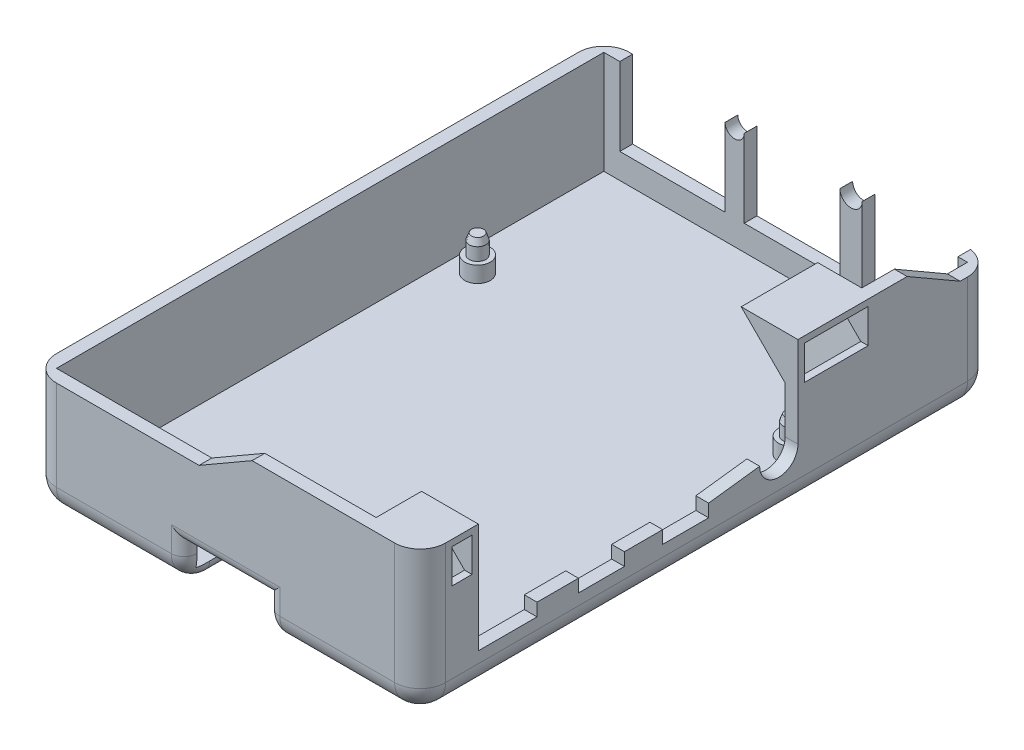
SolidWorks part; units mm, degrees
ref_plane "Płaszczyzna przednia" through (0, 0, 0) normal (0, 0, 1) x (1, 0, 0)
ref_plane "Płaszczyzna górna" through (0, 0, 0) normal (0, 1, 0) x (1, 0, 0)
ref_plane "Płaszczyzna prawa" through (0, 0, 0) normal (1, 0, 0) x (0, 0, -1)
sketch "Szkic1" plane through (0, 0, 0) normal (0, 1, 0) x (1, 0, 0)
  line L0 (-28.5, 42.9) -> (-30.5, 42.9) construction
  line L1 (-28.1, -42.5) -> (28.1, -42.5)
  line L2 (-28.1, -42.5) -> (-28.1, 42.5)
  line L3 (-28.1, 42.5) -> (28.1, 42.5)
  line L4 (28.1, -42.5) -> (28.1, 42.5)
  line L5 (-28.1, -42.5) -> (28.1, 42.5) construction
  line L6 (-28.1, 42.5) -> (28.1, -42.5) construction
  line L7 (28.5, -42.9) -> (-28.5, -42.9)
  line L8 (28.5, -42.9) -> (28.5, 42.9)
  line L9 (28.5, 42.9) -> (-28.5, 42.9)
  line L10 (-28.5, -42.9) -> (-28.5, 42.9)
  line L11 (28.5, -42.9) -> (-28.5, 42.9) construction
  line L12 (28.5, 42.9) -> (-28.5, -42.9) construction
  line L13 (30.5, -44.9) -> (-30.5, -44.9)
  line L14 (30.5, -44.9) -> (30.5, 44.9)
  line L15 (30.5, 44.9) -> (-30.5, 44.9)
  line L16 (-30.5, -44.9) -> (-30.5, 44.9)
  line L17 (30.5, -44.9) -> (-30.5, 44.9) construction
  line L18 (30.5, 44.9) -> (-30.5, -44.9) construction
  line L19 (-28.5, 42.9) -> (-28.5, 44.9) construction
  line L20 (-28.1, 42.5) -> (-28.1, 42.9) construction
  line L21 (-28.1, 42.5) -> (-28.5, 42.5) construction
  point P0 (0, 0)
  point P6 (0, 0)
  point P12 (0, 0)
  dimension "D1" = 56.2
  dimension "D2" = 85
  dimension "D3" = 2
  dimension "D4" = 0.4
extrude "Dodanie-wyciągnięcie2" add sketch "Szkic1" along normal blind 2 contours L1 L4 L3 L2 region at (0, 0, 0)
sketch "Szkic2" plane through (0, 2, 0) normal (0, 1, 0) x (1, 0, 0)
  line L0 (-24.575, -40.975) -> (-24.575, -42.5) construction
  line L1 (-28.1, -42.5) -> (28.1, -42.5) construction
  line L2 (-26.575, -38.975) -> (-28.1, -38.975) construction
  line L3 (-28.1, -42.5) -> (-28.1, 42.5) construction
  line L4 (24.575, -40.975) -> (24.575, -42.5) construction
  line L5 (26.575, -38.975) -> (28.1, -38.975) construction
  line L6 (28.1, -42.5) -> (28.1, 42.5) construction
  line L7 (-26.575, 19.175) -> (-28.1, 19.175) construction
  line L8 (26.575, 19.175) -> (28.1, 19.175) construction
  line L9 (-24.575, 19.175) -> (24.575, 19.175) construction
  line L10 (24.575, 19.175) -> (24.575, -38.975) construction
  circle A0 centre (-24.575, -38.975) radius 2
  circle A1 centre (24.575, -38.975) radius 2
  circle A2 centre (-24.575, 19.175) radius 2
  circle A3 centre (24.575, 19.175) radius 2
  dimension "D2" = 4
  dimension "D3" = 3.525
  dimension "D1" = 58.15
extrude "Dodanie-wyciągnięcie5" add sketch "Szkic2" along normal blind 2.5 contours A2 | A3 | A1 | A0
sketch "Szkic4" plane through (0, 4.5, 0) normal (0, 1, 0) x (1, 0, 0)
  line L0 (0, -38.975) -> (0, 19.175) construction
  line L1 (-24.575, -38.975) -> (24.575, -38.975) construction
  line L2 (-24.575, -38.975) -> (-24.575, 19.175) construction
  line L3 (-24.575, 19.175) -> (24.575, 19.175) construction
  line L4 (24.575, -38.975) -> (24.575, 19.175) construction
  line L5 (24.575, -9.9) -> (-24.575, -9.9) construction
  circle A0 centre (-24.575, 19.175) radius 1.3
  point P8 (0, -8.6)
  point P15 (0, -9.9)
  dimension "D1" = 2.6
extrude "Dodanie-wyciągnięcie6" add sketch "Szkic4" along normal blind 2 contours A0 | A0 region at (-24.575, 4.5, -19.175)
sketch "Szkic6" plane through (0, 6.5, 0) normal (0, 1, 0) x (1, 0, 0)
  circle A0 centre (-24.575, 19.175) radius 1.3
  circle A1 centre (-24.575, 19.175) radius 1.3 construction
  circle M3 centre (-24.575, 19.175) radius 1.3
extrude "Dodanie-wyciągnięcie7" add sketch "Szkic6" along normal blind 1 draft 20 contours M3 | A0 region at (-24.575, 6.5, -19.175)
extrude "Dodanie-wyciągnięcie3" add sketch "Szkic1<4>" along normal up to surface (2 mm away) contours L10 L7 L8 L9 L4 L1 L2 L3 region at (0, 0, 42.797) up to face at (-24.575, 2, 40.975)
sketch "Szkic1<4>" plane through (0, 0, 0) normal (0, 1, 0) x (1, 0, 0) same geometry as "Szkic1"
extrude "Dodanie-wyciągnięcie4" add sketch "Szkic1<5>" along normal up to surface (4.5 mm away) contours L16 L13 L14 L15 L7 L10 L9 L8 region at (0, 0, 43.8144) up to face at (-24.575, 4.5, 40.975)
sketch "Szkic1<5>" plane through (0, 0, 0) normal (0, 1, 0) x (1, 0, 0) same geometry as "Szkic1"
mirror "Lustro1" about plane through (0, 0, 0) normal (1, 0, 0) of "Dodanie-wyciągnięcie7", "Dodanie-wyciągnięcie6"
ref_plane "Płaszczyzna miedzy kolkami" through (0, 0, 9.9) normal (0, 0, 1) x (1, 0, 0)
mirror "Lustro2" about plane through (0, 0, 9.9) normal (0, 0, 1) of "Dodanie-wyciągnięcie7", "Lustro1", "Dodanie-wyciągnięcie6"
sketch "Szkic12" plane through (0, 0, 44.9) normal (0, 0, 1) x (1, 0, 0)
  line L0 (30.5, 0) -> (-30.5, 0) construction
  line L1 (-6.5, 0) -> (6.5, 0)
  line L2 (-6.5, 0) -> (-6.5, 4.5)
  line L3 (-6.5, 4.5) -> (6.5, 4.5)
  line L4 (6.5, 0) -> (6.5, 4.5)
  line L5 (30.5, 4.5) -> (-30.5, 4.5) construction
  line L6 (-6.5, 2.25) -> (-30.5, 2.25) construction
  line L7 (-30.5, 4.5) -> (-30.5, 0) construction
  line L8 (6.5, 2.25) -> (30.5, 2.25) construction
  line L9 (30.5, 4.5) -> (30.5, 0) construction
  dimension "D1" = 13
extrude "Wytnij-wyciągnięcie4" cut sketch "Szkic12" against normal blind 10
sketch "Szkic13" plane through (0, 4.5, 0) normal (0, 1, 0) x (1, 0, 0)
  line L12 (-6.5, -44.9) -> (-6.5, -42.9)
  line L13 (-6.5, -42.9) -> (-28.5, -42.9)
  line L14 (-28.5, -42.9) -> (-28.5, 42.9)
  line L15 (-28.5, 42.9) -> (28.5, 42.9)
  line L16 (28.5, 42.9) -> (28.5, -42.9)
  line L17 (28.5, -42.9) -> (6.5, -42.9)
  line L18 (6.5, -42.9) -> (6.5, -44.9)
  line L19 (6.5, -44.9) -> (30.5, -44.9)
  line L20 (30.5, -44.9) -> (30.5, 44.9)
  line L21 (30.5, 44.9) -> (-30.5, 44.9)
  line L22 (-30.5, 44.9) -> (-30.5, -44.9)
  line L23 (-30.5, -44.9) -> (-6.5, -44.9)
  line L24 (-6.5, -44.9) -> (-6.5, -42.9)
  line L25 (-6.5, -42.9) -> (-28.5, -42.9)
  line L26 (-28.5, -42.9) -> (-28.5, 42.9)
  line L27 (-28.5, 42.9) -> (28.5, 42.9)
  line L28 (28.5, 42.9) -> (28.5, -42.9)
  line L29 (28.5, -42.9) -> (6.5, -42.9)
  line L30 (6.5, -42.9) -> (6.5, -44.9)
  line L31 (6.5, -44.9) -> (30.5, -44.9)
  line L32 (30.5, -44.9) -> (30.5, 44.9)
  line L33 (30.5, 44.9) -> (-30.5, 44.9)
  line L34 (-30.5, 44.9) -> (-30.5, -44.9)
  line L35 (-30.5, -44.9) -> (-6.5, -44.9)
  dimension "D1" = 0
extrude "Dodanie-wyciągnięcie8" add sketch "Szkic13" along normal blind 1.45 contours L24 L25 L26 L27 L28 L29 L30 L31 L32 L33 L34 L35
sketch "Szkic14" plane through (0, 5.95, 0) normal (0, 1, 0) x (1, 0, 0)
  line L1 (-30.5, -44.9) -> (30.5, -44.9)
  line L2 (-30.5, -44.9) -> (-30.5, 44.9)
  line L3 (-30.5, 44.9) -> (30.5, 44.9)
  line L4 (30.5, -44.9) -> (30.5, 44.9)
  line L5 (-28.5, -42.9) -> (28.5, -42.9)
  line L6 (-28.5, -42.9) -> (-28.5, 42.9)
  line L7 (-28.5, 42.9) -> (28.5, 42.9)
  line L8 (28.5, -42.9) -> (28.5, 42.9)
extrude "Dodanie-wyciągnięcie9" add sketch "Szkic14" along normal blind 17
sketch "Szkic15" plane through (0, 0, -44.9) normal (0, 0, -1) x (-1, 0, 0)
  line L0 (-30.5, 22.95) -> (30.5, 22.95) construction
  line L1 (-27, 22.95) -> (26, 22.95)
  line L2 (-27, 22.95) -> (-27, 5.95)
  line L3 (-27, 5.95) -> (26, 5.95)
  line L4 (26, 22.95) -> (26, 5.95)
  line L5 (-27, 5.95) -> (-30.5, 5.95) construction
  line L6 (-30.5, 22.95) -> (-30.5, 0) construction
  line L7 (9.5, 5.95) -> (9.5, 22.95)
  line L8 (30.5, 22.95) -> (30.5, 0) construction
  line L9 (-30.5, 4.5) -> (30.5, 4.5) construction
  line L10 (-22.575, 4.5) -> (-26.575, 4.5) construction
  line L11 (6.5, 5.95) -> (6.5, 22.95)
  line L12 (-12, 5.95) -> (-12, 22.95)
  line L13 (-8.5, 5.95) -> (-8.5, 22.95)
  line L14 (-27, 14.45) -> (-12, 14.45) construction
  line L15 (-8.5, 14.45) -> (6.5, 14.45) construction
  line M9 (30.5, 22.95) -> (-30.5, 22.95)
  dimension "D1" = 3.5
  dimension "D2" = 1.45
  dimension "D3" = 4.5
  dimension "D4" = 16.5
  dimension "D5" = 15
  dimension "D6" = 3.5
extrude "Wytnij-wyciągnięcie5" cut sketch "Szkic15" against normal up to surface (2 mm away) contours L7 L3 L4 M9 | L13 L3 L11 M9 | L3 L12 L1 L2 region at (19.5, 14.45, -44.9) region at (1, 14.45, -44.9) region at (-17.75, 14.45, -44.9) up to face at (0, 12.475, -42.9)
sketch "Szkic16" plane through (30.5, 0, 0) normal (1, 0, 0) x (0, 0, -1)
  line L0 (-44.9, 22.95) -> (44.9, 22.95) construction
  line L1 (-36.975, 22.95) -> (17.175, 22.95)
  line L2 (-36.975, 22.95) -> (-36.975, 5.75)
  line L3 (-36.975, 5.75) -> (17.175, 5.75)
  line L4 (17.175, 22.95) -> (17.175, 5.75)
  line L5 (-36.975, 2) -> (-36.975, 4.5) construction
  line L6 (17.175, 4.5) -> (17.175, 2) construction
  line L7 (-36.975, 5.75) -> (-36.975, 4.5) construction
  line L8 (-36.975, 4.5) -> (17.175, 4.5) construction
  line L9 (17.175, 4.5) -> (17.175, 5.75) construction
  line L10 (21.175, 4.5) -> (17.175, 4.5) construction
  line L11 (-35.775, 5.75) -> (-35.775, 22.95)
  line L12 (-26.575, 5.75) -> (-26.575, 22.95)
  line L13 (-20.075, 5.75) -> (-20.075, 22.95)
  line L14 (-12.875, 5.75) -> (-12.875, 22.95)
  line L15 (-6.875, 5.75) -> (-6.875, 22.95)
  line L16 (0.325, 5.75) -> (0.325, 22.95)
  line L17 (8.325, 5.75) -> (8.325, 22.95)
  line L18 (14.325, 5.75) -> (14.325, 22.95)
  line L19 (17.175, 5.75) -> (-36.975, 5.75) construction
  line L20 (17.175, 11.75) -> (-36.975, 11.75)
  line L21 (-36.975, 9.75) -> (17.175, 9.75)
  line L22 (-36.975, 7.75) -> (17.175, 7.75)
  line L23 (-37.975, 7.75) -> (-37.975, 9.75) construction
  line L24 (-37.975, 7.75) -> (-37.975, 5.75) construction
  line L25 (0.325, 7.75) -> (8.325, 8.75)
  circle A0 centre (11.325, 8.75) radius 3
  point P42 (0.325, 7.75)
  dimension "D1" = 1.25
  dimension "D2" = 9.2
  dimension "D3" = 7.2
  dimension "D4" = 7.2
  dimension "D5" = 6
  dimension "D6" = 1.2
  dimension "D7" = 6.5
  dimension "D8" = 6
  dimension "D9" = 8
  dimension "D10" = 0
  dimension "D11" = 4
  dimension "D12" = 1
extrude "Wytnij-wyciągnięcie6" cut sketch "Szkic16" against normal up to surface (2 mm away) contours L20 L12 L1 L11 | L11 L21 L12 L20 | L11 L22 L12 L21 | L22 L11 L3 L12 | L20 L14 L1 L13 | L13 L21 L14 L20 | L13 L22 L14 L21 | L22 L13 L3 L14 | L20 L16 L1 L15 | L15 L21 L16 L20 | L15 L22 L16 L21 | L22 L15 L3 L16 | L20 L17 L1 L16 | L16 L21 L17 L20 | L16 L25 L17 L21 | L20 L15 L1 L14 | L14 L21 L15 L20 | L14 L22 L15 L21 | L20 L13 L1 L12 | L12 L21 L13 L20 | L12 L22 L13 L21 | L21 A0 L22 | L21 A0 | L22 A0 | A0 L20 L17 L21 | A0 L21 L18 L20 | L20 L18 L1 L17 | A0 L18 L21 | A0 L21 L17 region at (30.5, 17.35, 31.175) region at (30.5, 17.35, 23.325) region at (30.5, 10.75, 31.175) region at (30.5, 17.35, 16.475) region at (30.5, 10.75, 23.325) region at (30.5, 8.75, 31.175) region at (30.5, 17.35, 9.875) region at (30.5, 10.75, 16.475) region at (30.5, 8.75, 23.325) region at (30.5, 6.75, 31.175) region at (30.5, 17.35, 3.275) region at (30.5, 10.75, 9.875) region at (30.5, 8.75, 16.475) region at (30.5, 17.35, -4.325) region at (30.5, 10.75, 3.275) region at (30.5, 8.75, 9.875) region at (30.5, 6.75, 16.475) region at (30.5, 17.35, -11.325) region at (30.5, 10.75, -4.325) region at (30.5, 8.75, 3.275) region at (30.5, 11.1275, -9.0138) region at (30.5, 8.9722, -3.8806) region at (30.5, 6.75, 3.275) region at (30.5, 11.1275, -13.6362) region at (30.5, 9.5015, -8.3762) region at (30.5, 10.5784, -11.325) region at (30.5, 9.5015, -14.2738) region at (30.5, 8.75, -11.325) region at (30.5, 6.9216, -11.325) up to face at (28.5, 12.475, 0)
sketch "Szkic17" plane through (-30.5, 0, 0) normal (-1, 0, 0) x (0, 0, 1)
  line L0 (-44.9, 22.95) -> (44.9, 22.95) construction
  line L1 (-42.9, 22.95) -> (44.9, 22.95)
  line L2 (-42.9, 22.95) -> (-42.9, 2)
  line L3 (-42.9, 2) -> (44.9, 2)
  line L4 (44.9, 22.95) -> (44.9, 2)
  line L5 (44.9, 22.95) -> (44.9, 0) construction
  line L6 (-42.9, 22.95) -> (-42.9, 2) construction
  line L8 (34.9, 2) -> (42.9, 2) construction
extrude "Wytnij-wyciągnięcie7" [suppressed] cut sketch "Szkic17" against normal up to surface (2 mm away) up to face at (-28.5, 12.475, 0)
fillet "Zaokrąglenie1" radius 4 9 edges at (-18.5, 0, 44.9) (18.5, 0, 44.9) (30.5, 0, 0) (-30.5, 0, 0) (0, 0, -44.9) (-30.5, 11.475, -44.9) (30.5, 11.475, -44.9) (30.5, 11.475, 44.9) (-30.5, 11.475, 44.9)
fillet "Zaokrąglenie2" radius 2 8 edges at (6.5, 4.975, 44.9) (-6.5, 4.975, 44.9) (-6.5, 0, 37.9) (0, 5.95, 44.9) (6.5, 0, 37.9) (6.5, 1.1716, 43.7284) (-6.5, 1.1716, 43.7284) (0, 0, 34.9)
sketch "Szkic18" plane through (0, 0, -14.325) normal (0, 0, 1) x (1, 0, 0)
  line L0 (28.5, 22.95) -> (21.6, 22.95)
  line L1 (21.6, 22.95) -> (28.5, 16.05)
  line L2 (28.5, 8.75) -> (28.5, 22.95) construction
  line L3 (28.5, 16.05) -> (28.5, 22.95)
  dimension "D1" = 6.9
  dimension "D2" = 45
extrude "Dodanie-wyciągnięcie10" add sketch "Szkic18" against normal blind 12
sketch "Szkic19" plane through (30.5, 0, 0) normal (1, 0, 0) x (0, 0, -1)
  line L0 (14.325, 21.95) -> (15.325, 21.95)
  line L1 (14.325, 8.75) -> (14.325, 22.95) construction
  line L2 (15.325, 21.95) -> (15.325, 22.95)
  line L3 (14.325, 22.95) -> (40.9, 22.95) construction
  line L5 (15.325, 21.95) -> (25.325, 21.95)
  line L6 (15.325, 21.95) -> (15.325, 16.6161)
  line L7 (15.325, 16.6161) -> (25.325, 16.6161)
  line L8 (25.325, 21.95) -> (25.325, 16.6161)
  dimension "D1" = 1
  dimension "D2" = 10
extrude "Wytnij-wyciągnięcie8" cut sketch "Szkic19" along direction (-1, 0, 0) on the side against the normal up to vertex (8.9 mm away) contours L8 L5 L6 L7 region at (30.5, 19.283, -20.325) up to point (21.6, 22.95, -14.325)
sketch "Szkic20" plane through (0, 0, -25.325) normal (0, 0, 1) x (1, 0, 0)
  line L4 (30.5, 11.95) -> (22.6, 11.95)
  line L6 (24.0142, 21.95) -> (29.3481, 16.6161)
  line L7 (23.3071, 22.6571) -> (28.641, 17.3232) construction
  line L8 (27.9339, 16.6161) -> (30.5, 16.6161)
  line L9 (30.5, 16.6161) -> (30.5, 21.95)
  line L10 (30.5, 21.95) -> (22.6, 21.95)
  line L11 (22.6, 21.95) -> (27.9339, 16.6161)
  line L12 (27.9339, 16.6161) -> (30.5, 16.6161)
  line L13 (30.5, 16.6161) -> (30.5, 21.95)
  line L14 (30.5, 21.95) -> (22.6, 21.95)
  line L15 (22.6, 21.95) -> (27.9339, 16.6161)
  line M6 (27.9339, 16.6161) -> (30.5, 16.6161)
  line M8 (30.5, 21.95) -> (22.6, 21.95)
  line M9 (22.6, 21.95) -> (27.9339, 16.6161)
  dimension "D1" = 0
  dimension "D2" = 10
  dimension "D3" = 1
extrude "Dodanie-wyciągnięcie11" add sketch "Szkic20" along normal up to surface (10 mm away) contours L6 M8 M9 M6 region at (25.9741, 19.283, -25.325) up to face at (27.8835, 19.283, -15.325)
sketch "Szkic22" plane through (0, 0, -44.9) normal (0, 0, -1) x (-1, 0, 0)
  line L1 (9.5, 5.95) -> (9.5, 22.95) construction
  line L3 (6.5, 22.95) -> (9.5, 22.95) construction
  line L4 (9.5, 22.95) -> (6.5, 22.95)
  line L5 (9.5, 18.1544) -> (9.5, 22.95)
  line L7 (30.5, 22.95) -> (30.5, 4) construction
  line L10 (28.5, 22.95) -> (-28.5, 22.95) construction
  line L12 (-8.5, 18.1544) -> (-12, 18.1544) construction
  line L13 (-8.5, 5.95) -> (-8.5, 22.95) construction
  line L14 (-12, 5.95) -> (-12, 22.95) construction
  line L15 (-8.5, 18.1544) -> (6.5, 18.1544)
  line L16 (6.5, 5.95) -> (6.5, 22.95) construction
  line L17 (6.5, 18.1544) -> (9.5, 18.1544)
  line L18 (9.5, 18.1544) -> (26, 18.1544)
  line L19 (26, 22.95) -> (26, 5.95) construction
  line L20 (26, 18.1544) -> (30.5, 18.1544)
  line L21 (-12, 18.1544) -> (-12, 22.95)
  line L22 (-12, 22.95) -> (-8.5, 22.95)
  line L23 (-8.5, 22.95) -> (-8.5, 18.1544)
  line L24 (6.5, 18.1544) -> (6.5, 22.95)
  line L25 (30.5, 18.1544) -> (30.5, 22.95)
  line L26 (30.5, 22.95) -> (26.5, 22.95) construction
  line L27 (30.5, 22.95) -> (26, 22.95)
  line L28 (26, 22.95) -> (26, 18.1544)
  circle A0 centre (-10.25, 18.1544) radius 1.75
  circle A1 centre (8, 18.1544) radius 1.5
  line M9 (9.5, 5.95) -> (9.5, 22.95)
  line M10 (9.5, 22.95) -> (6.5, 22.95)
  line M11 (6.5, 22.95) -> (6.5, 5.95)
  line M13 (-8.5, 5.95) -> (-8.5, 22.95)
  line M14 (-8.5, 22.95) -> (-12, 22.95)
  line M15 (-12, 22.95) -> (-12, 5.95)
  dimension "D1" = 4.7956
extrude "Wytnij-wyciągnięcie10" cut sketch "Szkic22" against normal up to surface (2 mm away) contours A0 M13 M14 M15 | A1 M9 M10 M11 | A0 | A1 | L20 L25 L27 L28 region at (-8, 21.1257, -44.9) region at (10.25, 21.2171, -44.9) up to face at (0.6875, 13.9563, -42.9)
sketch "Szkic23" plane through (-30.5, 0, 0) normal (-1, 0, 0) x (0, 0, 1)
  line L0 (-42.9, 18.1544) -> (44.9, 18.1544)
  line L1 (44.9, 22.95) -> (44.9, 4) construction
  line L2 (44.9, 18.1544) -> (44.9, 22.95)
  line L3 (44.9, 22.95) -> (-42.9, 22.95)
  line L4 (-42.9, 22.95) -> (-42.9, 18.1544)
  point P9 (0, 0)
extrude "Wytnij-wyciągnięcie11" cut sketch "Szkic23" against normal up to surface (2 mm away) up to face at (-28.5, 13.6109, -8.58)
sketch "Szkic27" plane through (30.5, 0, 0) normal (1, 0, 0) x (0, 0, -1)
  line L2 (16.325, 14.6161) -> (40.9, 14.6161)
  line L3 (40.9, 4) -> (40.9, 22.95) construction
  line L4 (40.9, 14.6161) -> (40.9, 4)
  line L5 (40.9, 4) -> (16.325, 4)
  line L6 (-40.9, 4) -> (40.9, 4) construction
  line L7 (16.325, 4) -> (16.325, 14.6161)
  line L8 (15.325, 16.6161) -> (25.325, 16.6161) construction
  line L12 (14.325, 8.75) -> (14.325, 22.95) construction
  dimension "D1" = 2
  dimension "D3" = 2
extrude "Wytnij-wyciągnięcie16" [suppressed] cut sketch "Szkic27" against normal up to surface (2 mm away) up to face at (28.5, 10.269, 5.4321)
sketch "Szkic28" plane through (0, 0, 44.9) normal (0, 0, 1) x (1, 0, 0)
  line L0 (-30.5, 18.1544) -> (30.5, 18.1544)
  line L1 (30.5, 22.95) -> (30.5, 4) construction
  line L2 (0, 18.1544) -> (0, 20.5522)
  line L3 (0, 20.5522) -> (0, 22.95)
  line L4 (-26.5, 22.95) -> (26.5, 22.95) construction
  line L5 (0, 20.5522) -> (4.1531, 22.95)
  line L6 (0, 20.5522) -> (-4.1531, 18.1544)
  line L7 (-28.5, 18.1544) -> (-28.5, 22.95)
  line L8 (-28.5, 22.95) -> (4.1531, 22.95)
  line M9 (26.5, 22.95) -> (-26.5, 22.95)
  line M10 (-26.5, 22.95) -> (-26.5, 4)
  dimension "D1" = 60
extrude "Wytnij-wyciągnięcie17" cut sketch "Szkic28" against normal up to surface (2 mm away) contours L8 L7 L0 M10 | L6 L3 L0 M9 M10 | L3 L5 M9 region at (-13.7339, 20.6174, 44.9) region at (-27.5, 20.5522, 44.9) region at (1.3844, 22.1507, 44.9) up to face at (-2.5903, 8.4661, 42.9)
sketch "Szkic29" plane through (0, 0, 42.9) normal (0, 0, -1) x (-1, 0, 0)
  line L3 (-28.5, 22.95) -> (-28.5, 16.05)
  line L4 (-28.5, 16.05) -> (-21.6, 22.95)
  line L5 (-21.6, 22.95) -> (-28.5, 22.95)
  line L6 (-28.5, 22.95) -> (-28.5, 16.05)
  line L7 (-28.5, 16.05) -> (-21.6, 22.95)
  line L8 (-21.6, 22.95) -> (-28.5, 22.95)
  dimension "D1" = 0
extrude "Dodanie-wyciągnięcie12" add sketch "Szkic29" along normal up to surface (7.125 mm away) up to face at (29.5, 14.35, 35.775)
sketch "Szkic30" plane through (30.5, 0, 0) normal (1, 0, 0) x (0, 0, -1)
  line L0 (15.325, 21.95) -> (25.325, 21.95) construction
  line L1 (-39.9, 21.95) -> (-36.775, 21.95)
  line L2 (-39.9, 21.95) -> (-39.9, 16.6161)
  line L3 (-39.9, 16.6161) -> (-36.775, 16.6161)
  line L4 (-36.775, 21.95) -> (-36.775, 16.6161)
  line L5 (15.325, 16.6161) -> (25.325, 16.6161) construction
  line L6 (-40.9, 21.95) -> (-39.9, 21.95) construction
  line L7 (-40.9, 22.95) -> (-40.9, 4) construction
  line L8 (-39.9, 21.95) -> (-39.9, 22.95) construction
  line L9 (-40.9, 22.95) -> (-35.775, 22.95) construction
  line L10 (-36.775, 21.95) -> (-35.775, 21.95) construction
  line L11 (-35.775, 5.75) -> (-35.775, 22.95) construction
extrude "Wytnij-wyciągnięcie18" cut sketch "Szkic30" against normal up to surface (7.9 mm away) up to face at (25.05, 19.5, 39.3375)
sketch "Szkic31" plane through (0, 0, 39.9) normal (0, 0, -1) x (-1, 0, 0)
  line L0 (-27.9339, 16.6161) -> (-22.6, 21.95)
  line L1 (-22.6, 21.95) -> (-24.0142, 21.95)
  line L2 (-24.0142, 21.95) -> (-29.3481, 16.6161)
  line L3 (-27.9339, 16.6161) -> (-30.5, 16.6161) construction
  line L5 (-29.3481, 16.6161) -> (-27.9339, 16.6161)
  dimension "D1" = 1
extrude "Dodanie-wyciągnięcie13" add sketch "Szkic31" along normal up to surface (3.125 mm away) contours L5 L0 L1 L2 up to face at (27.8835, 19.283, 36.775)
sketch "Szkic32" plane through (30.5, 0, 0) normal (1, 0, 0) x (0, 0, -1)
  line L0 (31.4437, 22.95) -> (39.75, 18.1544)
  line L1 (14.325, 22.95) -> (40.9, 22.95) construction
  line L2 (42.9, 18.1544) -> (44.9, 18.1544) construction
  line L3 (44.8686, 18.1544) -> (39.75, 18.1544)
  line L5 (31.4437, 22.95) -> (26.325, 22.95) construction
  line L6 (26.325, 22.95) -> (26.325, 18.1544) construction
  line L7 (26.325, 18.1544) -> (39.75, 18.1544) construction
  line L8 (31.4437, 22.95) -> (44.8686, 22.95)
  line L9 (44.8686, 22.95) -> (44.8686, 18.1544)
  line L11 (44.8686, 22.95) -> (44.8686, 5.95) construction
  line L12 (35.5968, 20.5522) -> (44.8686, 20.5522) construction
  line L13 (35.5968, 20.5522) -> (26.325, 20.5522) construction
  dimension "D1" = 30
extrude "Wytnij-wyciągnięcie19" cut sketch "Szkic32" against normal up to surface (3.5 mm away) up to face at (27, 14.45, -43.8843)
